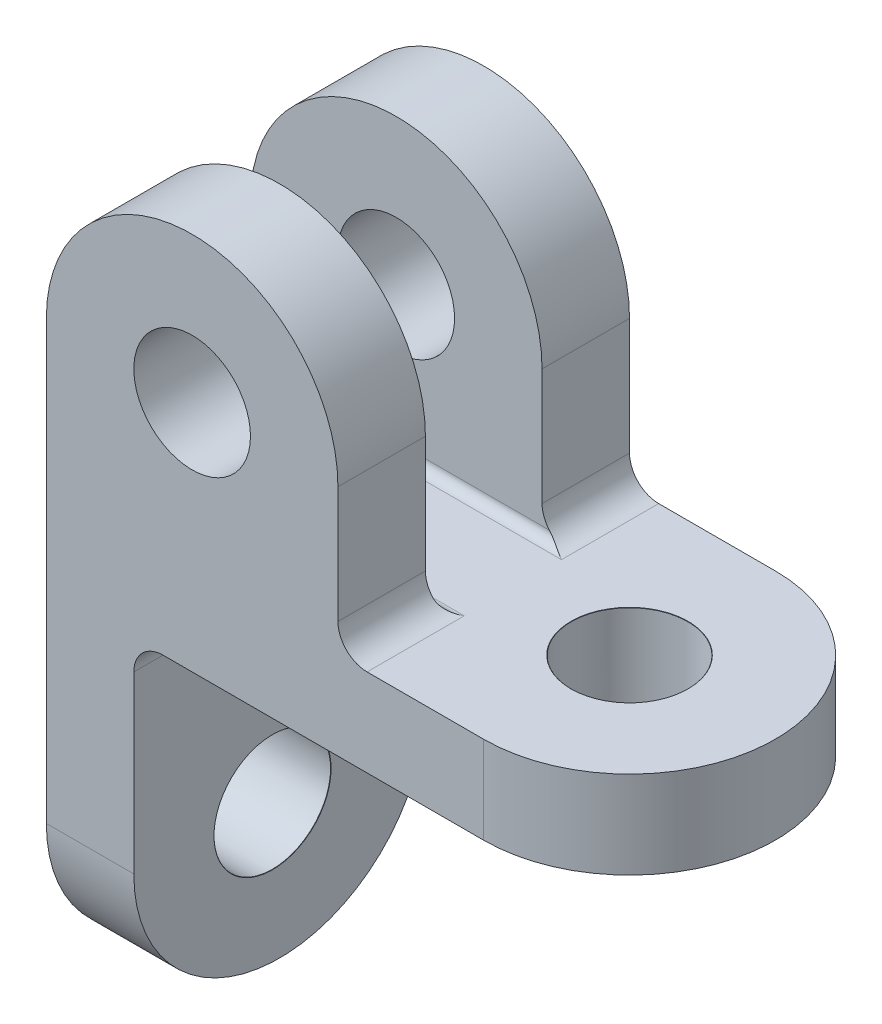
SolidWorks part; units mm, degrees
ref_plane "Front Plane" through (0, 0, 0) normal (0, 0, 1) x (1, 0, 0)
ref_plane "Top Plane" through (0, 0, 0) normal (0, 1, 0) x (1, 0, 0)
ref_plane "Right Plane" through (0, 0, 0) normal (1, 0, 0) x (0, 0, -1)
sketch "Sketch1" plane through (0, 0, 0) normal (0, 0, 1) x (1, 0, 0)
  line L5 (0, 0) -> (0, 60)
  line L6 (30, 60) -> (30, 45)
  line L7 (30, 45) -> (60, 45)
  line L8 (60, 45) -> (60, 36)
  line L9 (60, 36) -> (9, 36)
  line L10 (9, 36) -> (9, 0)
  line L11 (9, 0) -> (0, 0)
  line L12 (30, 45) -> (0, 45)
  arc A0 (0, 60) -> (30, 60) centre (15, 60) cw
  circle A1 centre (15, 60) radius 6
  dimension "D2" = 60
  dimension "D5" = 15
  dimension "D7" = 12
  dimension "D1" = 9
  dimension "D3" = 15
  dimension "D4" = 9
  dimension "D6" = 30
extrude "Boss-Extrude1" add sketch "Sketch1" along normal mid plane 30 contours L7 L12 L5 L11 L10 L9 L8 region at (0.75, 22.5, 0)
extrude "Boss-Extrude2" add sketch "Sketch1<3>" along normal blind 9 from offset 6 contours A0 L5 L12 L6 A1 region at (0.4243, 52.5, 0)
sketch "Sketch1<3>" plane through (0, 0, 0) normal (0, 0, 1) x (1, 0, 0) same geometry as "Sketch1"
extrude "Boss-Extrude3" add sketch "Sketch1<4>" against normal blind 9 from offset 6 contours A0 L5 L12 L6 A1 region at (0.4243, 52.5, 0) offset against normal yes
sketch "Sketch1<4>" plane through (0, 0, 0) normal (0, 0, 1) x (1, 0, 0) same geometry as "Sketch1"
fillet "Fillet1" 2 edges at (60, 40.5, 15) (60, 40.5, -15) type full round first side face at (24.75, 37.125, 15) second side face at (24.75, 37.125, -15) middle face at (60, 40.5, 0)
fillet "Fillet2" 2 edges at (4.5, 0, 15) (4.5, 0, -15) type full round first side face at (21, 37.125, 15) second side face at (21, 37.125, -15) middle face at (4.5, 0, 0)
hole_wizard "Ø12.0mm Dowel Hole1" positions "3DSketch1" profile "Sketch2" hole size "Ø12.0" standard "ISO" end condition up to next
sketch3d "3DSketch1"
  line L0 (45, 45, 0) -> (45, 36, 0) construction
  point P0 (9, 14.2626, 0.7285)
  point P2 (45, 45, 0)
sketch "Sketch2" plane through (9, 14.2626, 0.7285) normal (0, 1, 0) x (0, 0, -1)
  line L0 (0, 0) -> (0, 9)
  line L1 (0, 9) -> (6, 9)
  line L2 (6, 9) -> (6, 0.025)
  line L3 (6, 0.025) -> (6.025, 0)
  line L5 (6.025, 0) -> (0, 0)
  line L6 (-6, 0.025) -> (-6.025, 0) construction
  line L11 (0, -6.35) -> (0, 107.95) construction
  dimension "Thru Hole Dia." = 12
  dimension "Thru Hole Depth" = 9
  dimension "Near C'Sink Dia." = 12.05
  dimension "Near C'Sink Angle" = 90
fillet "Fillet3" radius 3 1 edges at (9, 36, 0)
fillet "Fillet4" radius 3 2 edges at (30, 45, -10.5) (30, 45, 10.5)
fillet "Fillet5" radius 1 2 edges at (16.5, 45, 6) (16.5, 45, -6)
